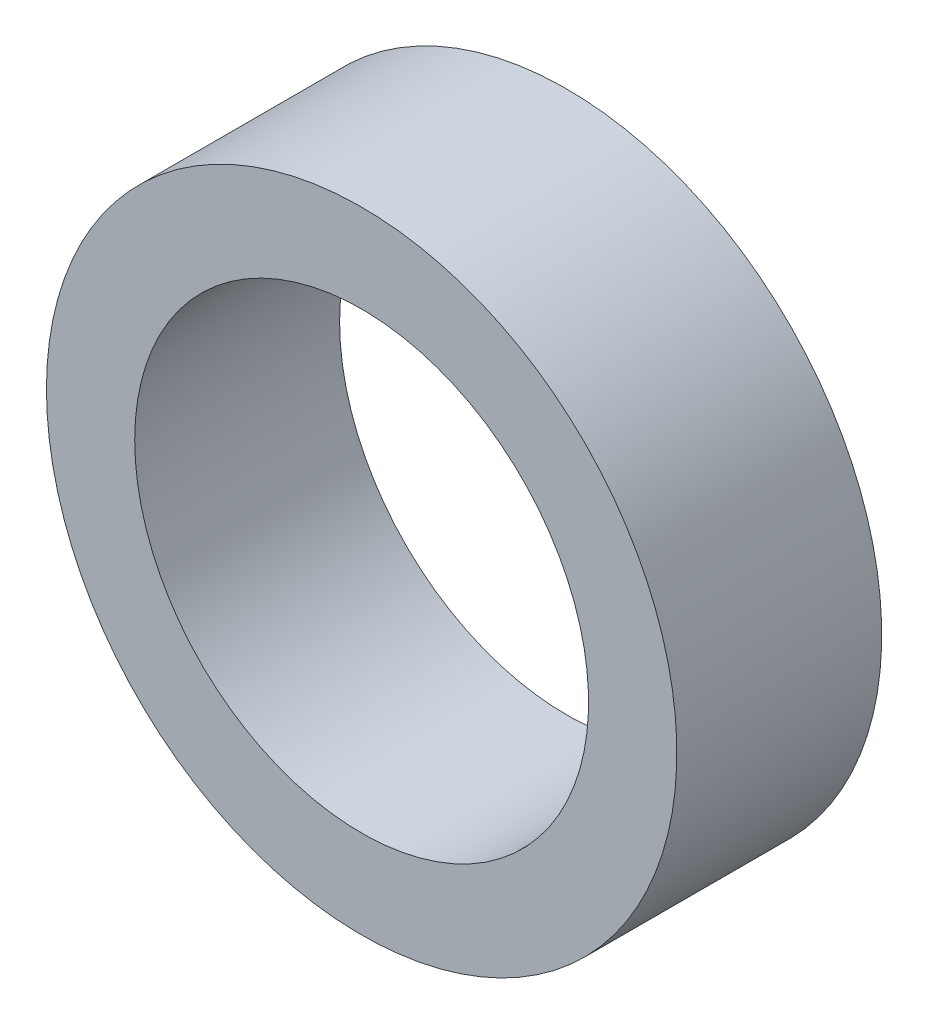
SolidWorks part; units mm, degrees
ref_plane "Front Plane" through (0, 0, 0) normal (0, 0, 1) x (1, 0, 0)
ref_plane "Top Plane" through (0, 0, 0) normal (0, 1, 0) x (1, 0, 0)
ref_plane "Right Plane" through (0, 0, 0) normal (1, 0, 0) x (0, 0, -1)
ref_axis "X" through (-88.99, 0, 0) along (1, 0, 0)
ref_axis "Y" through (0, 55, 0) along (0, -1, 0)
ref_axis "Z" through (0, 0, -88.99) along (0, 0, 1)
sketch "Sketch1" plane through (0, 0, 0) normal (0, 0, 1) x (1, 0, 0)
  circle A0 centre (0, 0) radius 3.6
  circle A1 centre (0, 0) radius 5
  dimension "D1" = 7.2
  dimension "D2" = 10
extrude "Boss-Extrude1" add sketch "Sketch1" along normal mid plane 3.25
